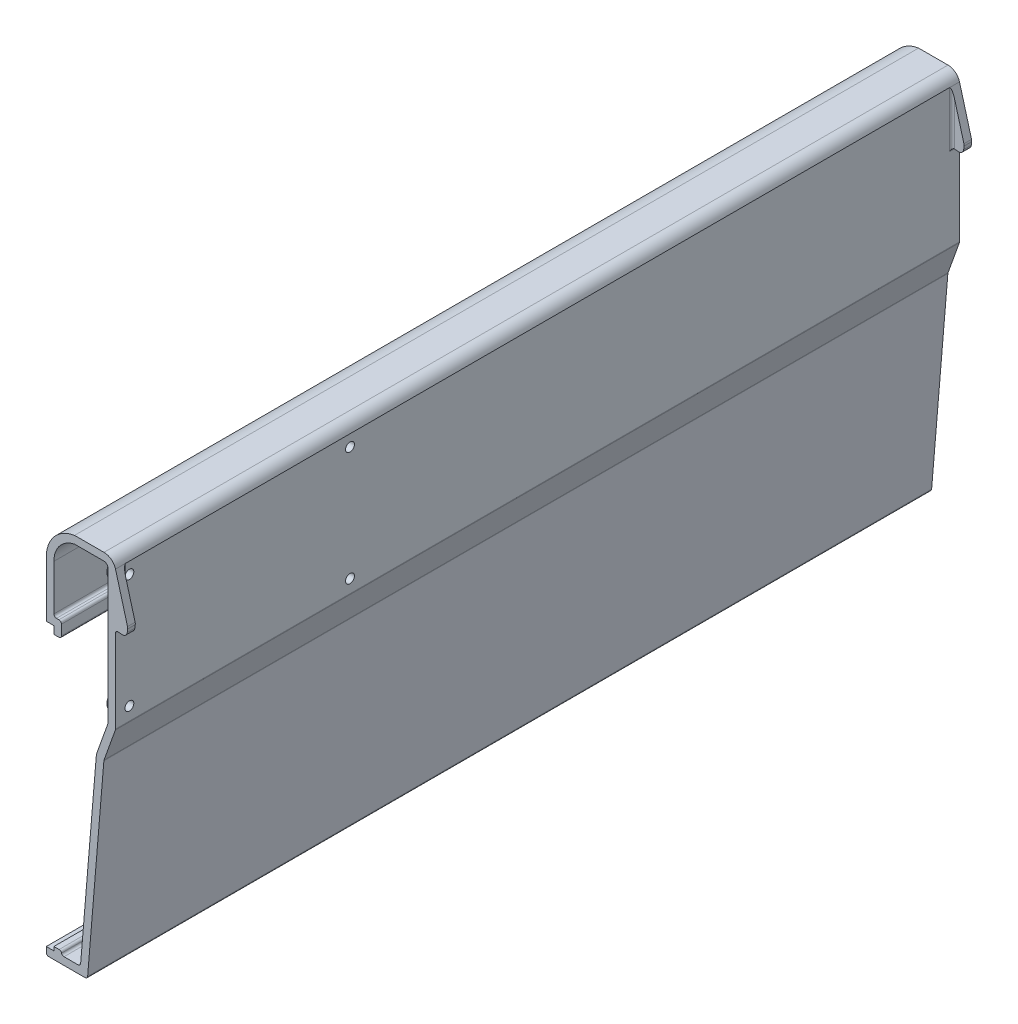
SolidWorks part; units mm, degrees
ref_plane "Front Plane" through (0, 0, 0) normal (0, 0, 1) x (1, 0, 0)
ref_plane "Top Plane" through (0, 0, 0) normal (0, 1, 0) x (1, 0, 0)
ref_plane "Right Plane" through (0, 0, 0) normal (1, 0, 0) x (0, 0, -1)
sketch "basecross" plane through (0, 0, 0) normal (0, 0, 1) x (1, 0, 0)
  line L0 (0, 977.3624) -> (0, 999.3624)
  line L1 (23.8396, 995.7004) -> (23.8396, 998.7004) construction
  line L2 (22.1346, 1008.8254) -> (20.6246, 1008.8254) construction
  line L4 (11.1719, 1012.3254) -> (22.7882, 1012.3254)
  line L5 (12.75, 867.2823) -> (12.75, 870.7823) construction
  line L6 (27.3396, 1008.856) -> (27.3396, 954.1413)
  line L7 (0, 866.1124) -> (0, 864.1124)
  line L9 (1, 863.1124) -> (15.3299, 863.1124)
  line L10 (27.2813, 953.8048) -> (22.7996, 941.2613)
  line L12 (22.7448, 941.0079) -> (16.3265, 864.0293)
  line L13 (0, 866.1124) -> (12.5696, 866.1124)
  line L14 (13.5662, 867.0293) -> (19.7878, 941.648)
  line L15 (19.8426, 941.9014) -> (24.2813, 954.3247)
  line L18 (0, 977.3624) -> (3, 977.3624)
  line L19 (3, 977.3624) -> (3, 999.3624)
  line L20 (11.1719, 1009.3254) -> (22.7882, 1009.3254)
  line L21 (24.3396, 954.6611) -> (24.3396, 1007.856)
  arc A0 (0, 999.3624) -> (11.1719, 1012.3254) centre (13.1065, 999.3624) cw
  arc A1 (22.7882, 1012.3254) -> (27.3396, 1008.856) centre (22.7882, 1007.6053) cw
  arc A2 (3, 999.3624) -> (11.1719, 1009.3254) centre (13.1592, 999.3624) cw
  arc A3 (22.7882, 1009.3254) -> (24.3396, 1007.856) centre (22.7882, 1007.7717) cw
  arc A4 (27.2813, 953.8048) -> (27.3396, 954.1413) centre (26.3396, 954.1413) ccw
  arc A5 (24.2813, 954.3247) -> (24.3396, 954.6611) centre (23.3396, 954.6611) ccw
  arc A6 (22.7996, 941.2613) -> (22.7448, 941.0079) centre (23.7413, 940.9248) ccw
  arc A7 (19.7878, 941.648) -> (19.8426, 941.9014) centre (20.7843, 941.5649) cw
  arc A8 (0, 864.1124) -> (1, 863.1124) centre (1, 864.1124) ccw
  arc A9 (15.3299, 863.1124) -> (16.3265, 864.0293) centre (15.3299, 864.1124) ccw
  arc A10 (12.5696, 866.1124) -> (13.5662, 867.0293) centre (12.5696, 867.1124) ccw
  point P42 (0, 863.1124)
  point P45 (16.25, 863.1124)
  point P48 (13.4897, 866.1124)
  dimension "D10" = 1
  dimension "D1" = 3.5
  dimension "D2" = 22
  dimension "D3" = 3
  dimension "D4" = 3.5
  dimension "D5" = 3.5
  dimension "D6" = 3
  dimension "D7" = 3
  dimension "D8" = 1
  dimension "D9" = 3
extrude "backprofile" add sketch "basecross" against normal up to surface (333.3625 mm away)
sketch "fpgascrewmount" plane through (24.3396, 0, 0) normal (-1, 0, 0) x (0, 0, 1)
  circle A0 centre (-92.6178, 1004.3254) radius 1.75
  circle A1 centre (-92.6178, 959.3254) radius 1.75
  circle A2 centre (-5.4778, 959.3254) radius 1.75
  circle A3 centre (-5.4778, 1004.3254) radius 1.75
  circle A4 centre (-92.6178, 1004.3254) radius 3.7
  circle A5 centre (-92.6178, 959.3254) radius 3.7
  circle A6 centre (-5.4778, 959.3254) radius 3.7
  circle A7 centre (-5.4778, 1004.3254) radius 3.7
extrude "fpgamount" add sketch "fpgascrewmount" along normal up to surface (2.205 mm away)
sketch "Sketch4" plane through (24.3396, 0, 0) normal (-1, 0, 0) x (0, 0, 1)
  circle A0 centre (-92.6178, 959.3254) radius 1.75
  circle A1 centre (-5.4778, 959.3254) radius 1.75
  circle A2 centre (-5.4778, 1004.3254) radius 1.75
  circle A3 centre (-92.6178, 1004.3254) radius 1.75
extrude "backholes" cut sketch "Sketch4" against normal up to surface (3 mm away) up to face at (27.3396, 981.4987, -166.6812)
sketch "Sketch6" plane through (0, 0, -333.3625) normal (0, 0, -1) x (-1, 0, 0)
  line L0 (-27.3396, 1008.856) -> (-32.0885, 991.5749)
  line L1 (-36.6372, 1026.5847) -> (-15.7369, 860.096) construction
  line L2 (-32.1445, 990.7958) -> (-31.9817, 989.4993)
  line L3 (-29.7482, 987.764) -> (-27.3396, 988.0664)
  line L4 (-27.3396, 1008.856) -> (-27.3396, 954.1413) construction
  line L5 (-27.3396, 988.0664) -> (-27.3396, 1008.856)
  arc A0 (-32.1445, 990.7958) -> (-32.0885, 991.5749) centre (-30.16, 991.045) cw
  arc A1 (-31.9817, 989.4993) -> (-29.7482, 987.764) centre (-29.9973, 989.7485) ccw
  point P11 (-32.1941, 991.1909)
  point P14 (-31.7326, 987.5149)
  dimension "D1" = 2
extrude "leftleg" add sketch "Sketch6" against normal blind 3
sketch "Sketch7" plane through (0, 0, 0) normal (0, 0, 1) x (1, 0, 0)
  line L0 (27.3396, 1008.856) -> (32.0885, 991.5749)
  line L2 (32.1445, 990.7958) -> (31.9817, 989.4993)
  line L4 (29.7482, 987.764) -> (27.3396, 988.0664)
  line L5 (27.3396, 988.0664) -> (27.3396, 1008.856)
  arc A0 (29.7482, 987.764) -> (31.9817, 989.4993) centre (29.9973, 989.7485) ccw
  arc A1 (32.1445, 990.7958) -> (32.0885, 991.5749) centre (30.16, 991.045) ccw
extrude "rightleg" add sketch "Sketch7" against normal blind 3
sketch "Sketch8" plane through (0, 866.1124, 0) normal (0, 1, 0) x (1, 0, 0)
  line L1 (3, 333.3625) -> (6, 333.3625)
  line L2 (3, 333.3625) -> (3, 0)
  line L3 (3, 0) -> (6, 0)
  line L4 (6, 333.3625) -> (6, 0)
  line L5 (0, 0) -> (11.1719, 0) construction
  dimension "D1" = 0
  dimension "D2" = 3
extrude "Boss-Extrude7" add sketch "Sketch8" along normal blind 1.5
fillet "Fillet1" radius 1 1 edges at (6, 866.1124, -166.6812)
sketch "Sketch9" plane through (3, 0, 0) normal (1, 0, 0) x (0, 0, -1)
  line L0 (333.365, 1026.5847) -> (333.365, 860.096) construction
  line L1 (0, 977.3624) -> (333.365, 977.3624)
  line L2 (0, 977.3624) -> (0, 980.3624)
  line L3 (0, 980.3624) -> (333.365, 980.3624)
  line L4 (333.365, 977.3624) -> (333.365, 980.3624)
  dimension "D1" = 3
extrude "Boss-Extrude8" add sketch "Sketch9" along normal blind 3
sketch "Sketch10" plane through (0, 977.3624, 0) normal (0, -1, 0) x (1, 0, 0)
  line L0 (3, -333.3625) -> (3, 0) construction
  line L1 (6, -333.365) -> (3, -333.365)
  line L2 (6, -333.365) -> (6, 0)
  line L3 (6, 0) -> (3, 0)
  line L4 (3, -333.365) -> (3, 0)
  line L5 (3, 0) -> (0, 0) construction
  dimension "D1" = 0
extrude "Boss-Extrude9" add sketch "Sketch10" along normal blind 3
fillet "Fillet2" radius 1 3 edges at (6, 974.3624, -166.6825) (6, 980.3624, -166.6825) (3, 980.3624, -166.6812)
fillet "Fillet3" radius 1 1 edges at (6, 867.6124, -166.6812)
fillet "Fillet4" radius 1 4 edges at (27.3396, 988.0664, -1.5) (27.3396, 988.0664, -331.8625) (27.3396, 998.4612, -330.3625) (27.3396, 998.4612, -3)
